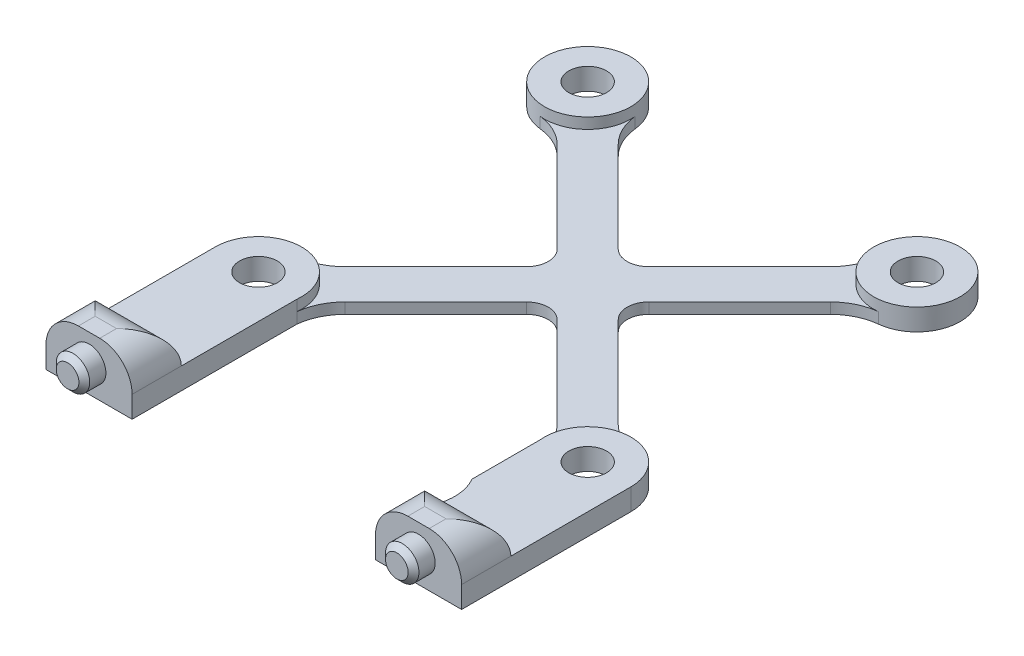
SolidWorks part; units mm, degrees
ref_plane "Front Plane" through (0, 0, 0) normal (0, 0, 1) x (1, 0, 0)
ref_plane "Top Plane" through (0, 0, 0) normal (0, 1, 0) x (1, 0, 0)
ref_plane "Right Plane" through (0, 0, 0) normal (1, 0, 0) x (0, 0, -1)
sketch "Sketch1" plane through (0, 0, 0) normal (0, 1, 0) x (1, 0, 0)
  line L0 (0, 9.8127) -> (0, -12.2658) construction
  line L1 (-32.8724, 0) -> (21.2608, 0) construction
  line L2 (-15.25, 15.25) -> (0, 15.25) construction
  line L3 (-15.25, 15.25) -> (-15.25, 0) construction
  line L4 (-15.25, 15.25) -> (15.25, -15.25) construction
  line L5 (-15.25, -15.25) -> (15.25, 15.25) construction
  line L6 (-16.6642, 13.8358) -> (13.8358, -16.6642)
  line L7 (-13.8358, -16.6642) -> (16.6642, 13.8358)
  line L8 (-13.8358, 16.6642) -> (16.6642, -13.8358)
  line L9 (-16.6642, -13.8358) -> (13.8358, 16.6642)
  circle A0 centre (-15.25, 15.25) radius 1.75
  circle A1 centre (15.25, 15.25) radius 1.75
  circle A2 centre (15.25, -15.25) radius 1.75
  circle A3 centre (-15.25, -15.25) radius 1.75
  circle A4 centre (-15.25, 15.25) radius 4
  circle A5 centre (15.25, 15.25) radius 4
  circle A6 centre (15.25, -15.25) radius 4
  circle A7 centre (-15.25, -15.25) radius 4
  dimension "D1" = 3.5
  dimension "D3" = 8
  dimension "D4" = 2
  dimension "D2" = 30.5
  dimension "D5" = 2
extrude "Boss-Extrude1" add sketch "Sketch1" along normal blind 1 contours A4 A0 | A4 L6 L9 L8 | A7 L7 L6 L9 | L9 L6 L7 L8 | A5 L9 L8 L7 | A6 L8 L7 L6 | A5 A1 | A6 A2 | A7 A3 region at (-6.9798, 0, -6.9798) region at (-18.3337, 0, -17.6162) region at (0, 0, 0) region at (-6.9798, 0, 6.9798) region at (6.9798, 0, 6.9798) region at (-12.5016, 0, 12.5016) region at (6.9798, 0, -6.9798) region at (12.5016, 0, 12.5016) region at (14.7427, 0, -19.1036)
sketch "Sketch2" plane through (0, 1, 0) normal (0, 1, 0) x (1, 0, 0)
  circle A4 centre (-15.25, 15.25) radius 4
  arc A5 (-11.3863, 14.2147) -> (-14.2147, 11.3863) centre (-15.25, 15.25) ccw construction
  circle A6 centre (15.25, 15.25) radius 4
  circle A7 centre (15.25, -15.25) radius 4
  circle A12 centre (-15.25, -15.25) radius 4
  arc A13 (-14.2147, -11.3863) -> (-11.3863, -14.2147) centre (-15.25, -15.25) ccw construction
  arc A14 (11.3863, -14.2147) -> (14.2147, -11.3863) centre (15.25, -15.25) ccw construction
  arc A15 (14.2147, 11.3863) -> (11.3863, 14.2147) centre (15.25, 15.25) ccw construction
  circle A16 centre (-15.25, -15.25) radius 1.75 construction
  circle A17 centre (15.25, -15.25) radius 1.75 construction
  circle A18 centre (15.25, 15.25) radius 1.75 construction
  circle A19 centre (-15.25, 15.25) radius 1.75 construction
  circle A20 centre (-15.25, -15.25) radius 1.75
  circle A21 centre (15.25, -15.25) radius 1.75
  circle A22 centre (15.25, 15.25) radius 1.75
  circle A23 centre (-15.25, 15.25) radius 1.75
  arc M19 (-11.3863, 14.2147) -> (-14.2147, 11.3863) centre (-15.25, 15.25) ccw
  arc M22 (-14.2147, -11.3863) -> (-11.3863, -14.2147) centre (-15.25, -15.25) ccw
  arc M25 (11.3863, -14.2147) -> (14.2147, -11.3863) centre (15.25, -15.25) ccw
  arc M28 (14.2147, 11.3863) -> (11.3863, 14.2147) centre (15.25, 15.25) ccw
  circle M31 centre (-15.25, 15.25) radius 1.75
  circle M32 centre (15.25, 15.25) radius 1.75
  circle M33 centre (15.25, -15.25) radius 1.75
  circle M34 centre (-15.25, -15.25) radius 1.75
extrude "Boss-Extrude2" add sketch "Sketch2" along normal offset from surface (1 mm away) 2 contours A4 M19 M31 | A12 M22 M34 | A7 M25 M33 | A6 M28 M32 region at (-11.3964, 1, -14.7427) region at (17.6162, 1, -12.1663) region at (14.7427, 1, 19.1036) region at (-18.3337, 1, 17.6162) up to face at (0, 0, 0)
fillet "Fillet1" radius 5 8 edges at (11.3863, 0.5, -14.2147) (14.2147, 0.5, 11.3863) (-14.2147, 0.5, 11.3863) (11.3863, 0.5, 14.2147) (14.2147, 0.5, -11.3863) (-11.3863, 0.5, 14.2147) (-11.3863, 0.5, -14.2147) (-14.2147, 0.5, -11.3863)
fillet "Fillet2" radius 2 4 edges at (0, 0.5, -2.8284) (2.8284, 0.5, 0) (0, 0.5, 2.8284) (-2.8284, 0.5, 0)
sketch "Sketch3" plane through (0, 0, 0) normal (0, -1, 0) x (1, 0, 0)
  line L0 (0, 20.9881) -> (0, -14.4185) construction
  line L1 (-25.1, 30.93) -> (25.1, 30.93) construction
  line L2 (-25.1, 30.93) -> (25.1, 30.93)
  line L3 (-11.2723, 15.6721) -> (-11.2723, 30.93)
  line L4 (-19.25, 15.25) -> (-19.25, 30.93)
  line L5 (11.2723, 15.6721) -> (11.2723, 30.93)
  line L6 (19.25, 15.25) -> (19.25, 30.93)
  line L8 (-9.8358, -12.6642) -> (-1.4142, -4.2426)
  line L9 (1.4142, -4.2426) -> (9.8358, -12.6642)
  line L10 (12.6642, -9.8358) -> (4.2426, -1.4142)
  line L11 (4.2426, 1.4142) -> (12.6642, 9.8358)
  line L12 (9.8358, 12.6642) -> (1.4142, 4.2426)
  line L13 (-1.4142, 4.2426) -> (-9.8358, 12.6642)
  line L14 (-12.6642, 9.8358) -> (-4.2426, 1.4142)
  line L15 (-4.2426, -1.4142) -> (-12.6642, -9.8358)
  line L16 (-9.8358, -12.6642) -> (-1.4142, -4.2426)
  line L17 (1.4142, -4.2426) -> (9.8358, -12.6642)
  line L18 (12.6642, -9.8358) -> (4.2426, -1.4142)
  line L19 (4.2426, 1.4142) -> (12.6642, 9.8358)
  line L20 (9.8358, 12.6642) -> (1.4142, 4.2426)
  line L21 (-1.4142, 4.2426) -> (-9.8358, 12.6642)
  line L22 (-12.6642, 9.8358) -> (-4.2426, 1.4142)
  line L23 (-4.2426, -1.4142) -> (-12.6642, -9.8358)
  arc A16 (-15.6721, -11.2723) -> (-11.2723, -15.6721) centre (-15.25, -15.25) ccw
  arc A17 (-9.8358, -12.6642) -> (-11.2723, -15.6721) centre (-6.3003, -16.1997) ccw
  arc A18 (1.4142, -4.2426) -> (-1.4142, -4.2426) centre (0, -5.6569) ccw
  arc A19 (11.2723, -15.6721) -> (9.8358, -12.6642) centre (6.3003, -16.1997) ccw
  arc A20 (11.2723, -15.6721) -> (15.6721, -11.2723) centre (15.25, -15.25) ccw
  arc A21 (12.6642, -9.8358) -> (15.6721, -11.2723) centre (16.1997, -6.3003) ccw
  arc A22 (4.2426, 1.4142) -> (4.2426, -1.4142) centre (5.6569, 0) ccw
  arc A23 (15.6721, 11.2723) -> (12.6642, 9.8358) centre (16.1997, 6.3003) ccw
  arc A24 (15.6721, 11.2723) -> (11.2723, 15.6721) centre (15.25, 15.25) ccw
  arc A25 (9.8358, 12.6642) -> (11.2723, 15.6721) centre (6.3003, 16.1997) ccw
  arc A26 (-1.4142, 4.2426) -> (1.4142, 4.2426) centre (0, 5.6569) ccw
  arc A27 (-11.2723, 15.6721) -> (-9.8358, 12.6642) centre (-6.3003, 16.1997) ccw
  arc A28 (-11.2723, 15.6721) -> (-15.6721, 11.2723) centre (-15.25, 15.25) ccw
  arc A29 (-12.6642, 9.8358) -> (-15.6721, 11.2723) centre (-16.1997, 6.3003) ccw
  arc A30 (-4.2426, -1.4142) -> (-4.2426, 1.4142) centre (-5.6569, 0) ccw
  arc A31 (-15.6721, -11.2723) -> (-12.6642, -9.8358) centre (-16.1997, -6.3003) ccw
  arc A32 (-15.6721, -11.2723) -> (-11.2723, -15.6721) centre (-15.25, -15.25) ccw
  arc A33 (-9.8358, -12.6642) -> (-11.2723, -15.6721) centre (-6.3003, -16.1997) ccw
  arc A34 (1.4142, -4.2426) -> (-1.4142, -4.2426) centre (0, -5.6569) ccw
  arc A35 (11.2723, -15.6721) -> (9.8358, -12.6642) centre (6.3003, -16.1997) ccw
  arc A36 (11.2723, -15.6721) -> (15.6721, -11.2723) centre (15.25, -15.25) ccw
  arc A37 (12.6642, -9.8358) -> (15.6721, -11.2723) centre (16.1997, -6.3003) ccw
  arc A38 (4.2426, 1.4142) -> (4.2426, -1.4142) centre (5.6569, 0) ccw
  arc A39 (15.6721, 11.2723) -> (12.6642, 9.8358) centre (16.1997, 6.3003) ccw
  arc A40 (15.6721, 11.2723) -> (11.2723, 15.6721) centre (15.25, 15.25) ccw
  arc A41 (9.8358, 12.6642) -> (11.2723, 15.6721) centre (6.3003, 16.1997) ccw
  arc A42 (-1.4142, 4.2426) -> (1.4142, 4.2426) centre (0, 5.6569) ccw
  arc A43 (-11.2723, 15.6721) -> (-9.8358, 12.6642) centre (-6.3003, 16.1997) ccw
  arc A44 (-11.2723, 15.6721) -> (-15.6721, 11.2723) centre (-15.25, 15.25) ccw
  arc A45 (-12.6642, 9.8358) -> (-15.6721, 11.2723) centre (-16.1997, 6.3003) ccw
  arc A46 (-4.2426, -1.4142) -> (-4.2426, 1.4142) centre (-5.6569, 0) ccw
  arc A47 (-15.6721, -11.2723) -> (-12.6642, -9.8358) centre (-16.1997, -6.3003) ccw
  arc M37 (15.6721, 11.2723) -> (11.2723, 15.6721) centre (15.25, 15.25) ccw
  arc M43 (-11.2723, 15.6721) -> (-15.6721, 11.2723) centre (-15.25, 15.25) ccw
  dimension "D1" = 0
extrude "Boss-Extrude3" add sketch "Sketch3" against normal up to surface (2 mm away) contours M37 | L4 L3 L2 M43 region at (-15.2637, 0, 24.6338) region at (15.2637, 0, 24.6338) up to face at (15.25, 2, 19.25)
sketch "Sketch4" plane through (0, 2, 0) normal (0, 1, 0) x (1, 0, 0)
  circle A0 centre (7.48, -24.18) radius 4.38
  circle A1 centre (7.48, -24.18) radius 3.88 construction
  dimension "D1" = 0.5
extrude "Cut-Extrude1" cut sketch "Sketch4" against normal up to next
sketch "Sketch5" plane through (0, 2, 0) normal (0, 1, 0) x (1, 0, 0)
  line L0 (-11.2723, -15.6721) -> (-11.2723, -30.93) construction
  line L1 (-19.25, -30.93) -> (-11.2723, -30.93)
  line L2 (-19.25, -30.93) -> (-19.25, -26.3715)
  line L3 (-19.25, -26.3715) -> (-11.2723, -26.3715)
  line L4 (-11.2723, -30.93) -> (-11.2723, -26.3715)
  line L6 (19.25, -30.93) -> (11.2723, -30.93)
  line L7 (19.25, -30.93) -> (19.25, -26.3715)
  line L8 (19.25, -26.3715) -> (11.2723, -26.3715)
  line L9 (11.2723, -30.93) -> (11.2723, -26.3715)
extrude "Boss-Extrude4" add sketch "Sketch5" along normal blind 3
sketch "Sketch6" plane through (0, 0, 30.93) normal (0, 0, 1) x (1, 0, 0)
  line L0 (-19.25, 2.5) -> (19.25, 2.5) construction
  line L1 (-19.25, 5) -> (-19.25, 0) construction
  line L2 (19.25, 5) -> (19.25, 0) construction
  line L3 (0, 0) -> (0, 2.5) construction
  circle A0 centre (-15.25, 2.5) radius 1.55
  circle A1 centre (15.25, 2.5) radius 1.55
  dimension "D1" = 30.5
  dimension "D2" = 3.1
extrude "Boss-Extrude5" add sketch "Sketch6" along normal blind 2
fillet "Fillet3" radius 3 6 edges at (19.25, 5, 28.6507) (11.2723, 5, 28.6507) (-11.2723, 5, 28.6507) (-19.25, 5, 28.6507) (15.2612, 5, 26.3715) (-15.2612, 5, 26.3715)
chamfer "Chamfer1" distance 0.5 angle 45 2 edges at (13.7, 2.5, 32.93) (-13.7, 2.5, 32.93)
sketch "Sketch7" [suppressed] plane through (0, 0, 0) normal (0, -1, 0) x (1, 0, 0)
  line L0 (-15.25, 32.93) -> (-15.25, 17) construction
  line L1 (-14.2, 32.93) -> (-16.3, 32.93) construction
  line L2 (0, 0) -> (0, 38.1559) construction
  line L3 (-19.25, 30.93) -> (-11.2723, 30.93) construction
  line L4 (-15.5, 32.93) -> (-15, 32.93)
  line L5 (-15.5, 32.93) -> (-15.5, 30.93)
  line L6 (-15.5, 30.93) -> (-15, 30.93)
  line L7 (-15, 32.93) -> (-15, 30.93)
  line L8 (-15.25, 32.93) -> (-15.25, 30.93) construction
  line L9 (15.5, 32.93) -> (15, 32.93)
  line L10 (15, 32.93) -> (15, 30.93)
  line L11 (15.5, 30.93) -> (15, 30.93)
  line L12 (15.5, 32.93) -> (15.5, 30.93)
  circle A0 centre (-15.25, 15.25) radius 1.75 construction
  dimension "D1" = 0.5
extrude "Boss-Extrude6" [suppressed] add sketch "Sketch7" against normal up to body
